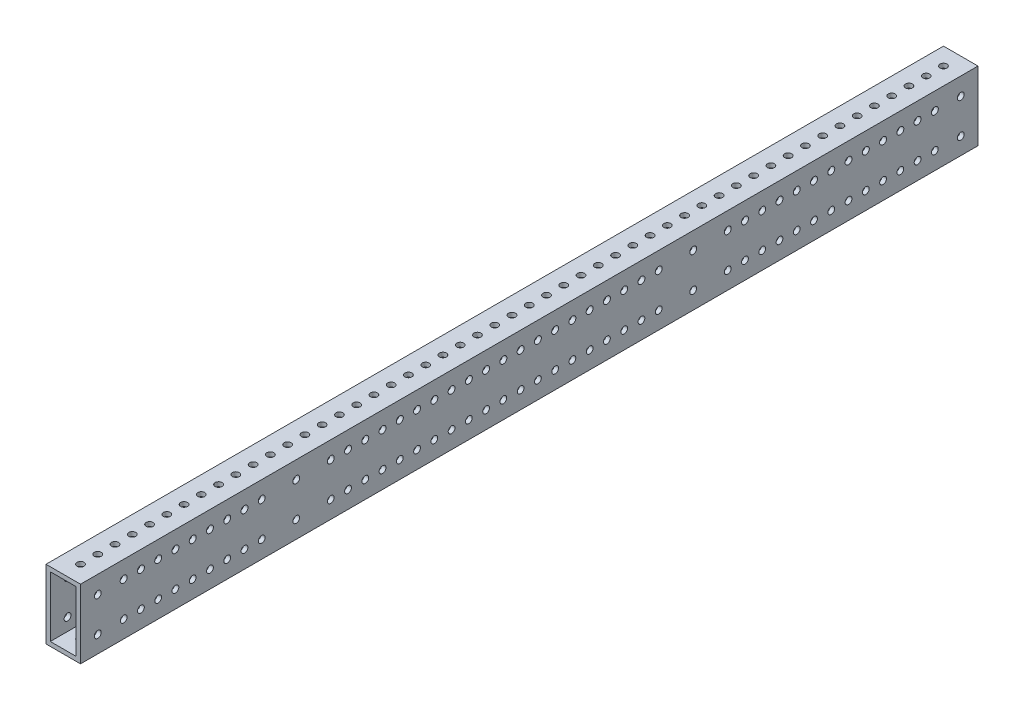
SolidWorks part; units mm, degrees
material "6061-T6 (SS)"
ref_plane "Front Plane" through (0, 0, 0) normal (0, 0, 1) x (1, 0, 0)
ref_plane "Top Plane" through (0, 0, 0) normal (0, 1, 0) x (1, 0, 0)
ref_plane "Right Plane" through (0, 0, 0) normal (1, 0, 0) x (0, 0, -1)
sketch "Sketch1" plane through (0, 0, 0) normal (0, 0, 1) x (1, 0, 0)
  line L0 (-9.525, 22.225) -> (9.525, 22.225)
  line L1 (-12.7, 25.4) -> (12.7, 25.4)
  line L2 (-12.7, 25.4) -> (-12.7, -25.4)
  line L3 (-12.7, -25.4) -> (12.7, -25.4)
  line L4 (12.7, 25.4) -> (12.7, -25.4)
  line L5 (9.525, 22.225) -> (9.525, -22.225)
  line L6 (-9.525, -22.225) -> (9.525, -22.225)
  line L7 (-9.525, 22.225) -> (-9.525, -22.225)
  line L8 (-12.7, 25.4) -> (12.7, -25.4) construction
  line L9 (12.7, 25.4) -> (-12.7, -25.4) construction
  point P5 (0, 0)
  dimension "D1" = 25.4
  dimension "D2" = 50.8
  dimension "D3" = 3.175
extrude "Boss-Extrude1" add sketch "Sketch1" along normal mid plane 660.4
sketch "Sketch2" plane through (0, 25.4, 0) normal (0, 1, 0) x (1, 0, 0)
  line L0 (12.7, -330.2) -> (-12.7, -330.2) construction
  line L1 (-12.7, -330.2) -> (-12.7, 330.2) construction
  line L4 (12.7, 330.2) -> (-12.7, 330.2) construction
  circle A0 centre (0, -317.5) radius 2.5527 construction
  circle A1 centre (25.4, -292.1) radius 2.5527 construction
  circle A2 centre (0, -317.5) radius 2.5527
  circle A3 centre (0, -304.8) radius 2.5527
  circle A4 centre (0, -304.8) radius 2.5527 construction
  circle A5 centre (25.4, -279.4) radius 2.5527 construction
  circle A6 centre (0, -292.1) radius 2.5527
  circle A7 centre (0, -292.1) radius 2.5527 construction
  circle A8 centre (25.4, -266.7) radius 2.5527 construction
  circle A9 centre (0, -279.4) radius 2.5527
  circle A10 centre (0, -279.4) radius 2.5527 construction
  circle A11 centre (25.4, -254) radius 2.5527 construction
  circle A12 centre (0, -266.7) radius 2.5527
  circle A13 centre (0, -266.7) radius 2.5527 construction
  circle A14 centre (25.4, -241.3) radius 2.5527 construction
  circle A15 centre (0, -254) radius 2.5527
  circle A16 centre (0, -254) radius 2.5527 construction
  circle A17 centre (25.4, -228.6) radius 2.5527 construction
  circle A18 centre (0, -241.3) radius 2.5527
  circle A19 centre (0, -241.3) radius 2.5527 construction
  circle A20 centre (25.4, -215.9) radius 2.5527 construction
  circle A21 centre (0, -228.6) radius 2.5527
  circle A22 centre (0, -228.6) radius 2.5527 construction
  circle A23 centre (25.4, -203.2) radius 2.5527 construction
  circle A24 centre (0, -215.9) radius 2.5527
  circle A25 centre (0, -215.9) radius 2.5527 construction
  circle A26 centre (25.4, -190.5) radius 2.5527 construction
  circle A27 centre (0, -203.2) radius 2.5527
  circle A28 centre (0, -203.2) radius 2.5527 construction
  circle A29 centre (25.4, -177.8) radius 2.5527 construction
  circle A30 centre (0, -190.5) radius 2.5527
  circle A31 centre (0, -190.5) radius 2.5527 construction
  circle A32 centre (25.4, -165.1) radius 2.5527 construction
  circle A33 centre (0, -177.8) radius 2.5527
  circle A34 centre (0, -177.8) radius 2.5527 construction
  circle A35 centre (25.4, -152.4) radius 2.5527 construction
  circle A36 centre (0, -165.1) radius 2.5527
  circle A37 centre (0, -165.1) radius 2.5527 construction
  circle A38 centre (25.4, -139.7) radius 2.5527 construction
  circle A39 centre (0, -152.4) radius 2.5527
  circle A40 centre (0, -152.4) radius 2.5527 construction
  circle A41 centre (25.4, -127) radius 2.5527 construction
  circle A42 centre (0, -139.7) radius 2.5527
  circle A43 centre (0, -139.7) radius 2.5527 construction
  circle A44 centre (25.4, -114.3) radius 2.5527 construction
  circle A45 centre (0, -127) radius 2.5527
  circle A46 centre (0, -127) radius 2.5527 construction
  circle A47 centre (25.4, -101.6) radius 2.5527 construction
  circle A48 centre (0, -114.3) radius 2.5527
  circle A49 centre (0, -114.3) radius 2.5527 construction
  circle A50 centre (25.4, -88.9) radius 2.5527 construction
  circle A51 centre (0, -101.6) radius 2.5527
  circle A52 centre (0, -101.6) radius 2.5527 construction
  circle A53 centre (25.4, -76.2) radius 2.5527 construction
  circle A54 centre (0, -88.9) radius 2.5527
  circle A55 centre (0, -88.9) radius 2.5527 construction
  circle A56 centre (25.4, -63.5) radius 2.5527 construction
  circle A57 centre (0, -76.2) radius 2.5527
  circle A58 centre (0, -76.2) radius 2.5527 construction
  circle A59 centre (25.4, -50.8) radius 2.5527 construction
  circle A60 centre (0, -63.5) radius 2.5527
  circle A61 centre (0, -63.5) radius 2.5527 construction
  circle A62 centre (25.4, -38.1) radius 2.5527 construction
  circle A63 centre (0, -50.8) radius 2.5527
  circle A64 centre (0, -50.8) radius 2.5527 construction
  circle A65 centre (25.4, -25.4) radius 2.5527 construction
  circle A66 centre (0, -38.1) radius 2.5527
  circle A67 centre (0, -38.1) radius 2.5527 construction
  circle A68 centre (25.4, -12.7) radius 2.5527 construction
  circle A69 centre (0, -25.4) radius 2.5527
  circle A70 centre (0, -25.4) radius 2.5527 construction
  circle A71 centre (25.4, 0) radius 2.5527 construction
  circle A72 centre (0, -12.7) radius 2.5527
  circle A73 centre (0, -12.7) radius 2.5527 construction
  circle A74 centre (25.4, 12.7) radius 2.5527 construction
  circle A75 centre (0, 0) radius 2.5527
  circle A76 centre (0, 0) radius 2.5527 construction
  circle A77 centre (25.4, 25.4) radius 2.5527 construction
  circle A78 centre (0, 12.7) radius 2.5527
  circle A79 centre (0, 12.7) radius 2.5527 construction
  circle A80 centre (25.4, 38.1) radius 2.5527 construction
  circle A81 centre (0, 25.4) radius 2.5527
  circle A82 centre (0, 25.4) radius 2.5527 construction
  circle A83 centre (25.4, 50.8) radius 2.5527 construction
  circle A84 centre (0, 38.1) radius 2.5527
  circle A85 centre (0, 38.1) radius 2.5527 construction
  circle A86 centre (25.4, 63.5) radius 2.5527 construction
  circle A87 centre (0, 50.8) radius 2.5527
  circle A88 centre (0, 50.8) radius 2.5527 construction
  circle A89 centre (25.4, 76.2) radius 2.5527 construction
  circle A90 centre (0, 63.5) radius 2.5527
  circle A91 centre (0, 63.5) radius 2.5527 construction
  circle A92 centre (25.4, 88.9) radius 2.5527 construction
  circle A93 centre (0, 76.2) radius 2.5527
  circle A94 centre (0, 76.2) radius 2.5527 construction
  circle A95 centre (25.4, 101.6) radius 2.5527 construction
  circle A96 centre (0, 88.9) radius 2.5527
  circle A97 centre (0, 88.9) radius 2.5527 construction
  circle A98 centre (25.4, 114.3) radius 2.5527 construction
  circle A99 centre (0, 101.6) radius 2.5527
  circle A100 centre (0, 101.6) radius 2.5527 construction
  circle A101 centre (25.4, 127) radius 2.5527 construction
  circle A108 centre (0, 127) radius 2.5527 [skipped]
  circle A109 centre (0, 127) radius 2.5527 [skipped]
  circle A110 centre (25.4, 152.4) radius 2.5527 [skipped]
  circle A111 centre (0, 114.3) radius 2.5527 [skipped]
  circle A112 centre (0, 114.3) radius 2.5527 [skipped]
  circle A113 centre (25.4, 139.7) radius 2.5527 [skipped]
  circle A114 centre (25.4, 139.7) radius 2.5527 construction
  circle A115 centre (0, 114.3) radius 2.5527 construction
  circle A116 centre (0, 114.3) radius 2.5527
  circle A117 centre (25.4, 152.4) radius 2.5527 construction
  circle A118 centre (0, 127) radius 2.5527 construction
  circle A119 centre (0, 127) radius 2.5527
  circle A120 centre (25.4, 165.1) radius 2.5527 construction
  circle A121 centre (0, 139.7) radius 2.5527 construction
  circle A122 centre (0, 139.7) radius 2.5527
  circle A123 centre (25.4, 177.8) radius 2.5527 construction
  circle A124 centre (0, 152.4) radius 2.5527 construction
  circle A125 centre (0, 152.4) radius 2.5527
  circle A126 centre (25.4, 190.5) radius 2.5527 construction
  circle A127 centre (0, 165.1) radius 2.5527 construction
  circle A128 centre (0, 165.1) radius 2.5527
  circle A129 centre (25.4, 203.2) radius 2.5527 construction
  circle A130 centre (0, 177.8) radius 2.5527 construction
  circle A131 centre (0, 177.8) radius 2.5527
  circle A132 centre (25.4, 215.9) radius 2.5527 construction
  circle A133 centre (0, 190.5) radius 2.5527 construction
  circle A134 centre (0, 190.5) radius 2.5527
  circle A135 centre (25.4, 228.6) radius 2.5527 construction
  circle A136 centre (0, 203.2) radius 2.5527 construction
  circle A137 centre (0, 203.2) radius 2.5527
  circle A138 centre (25.4, 241.3) radius 2.5527 construction
  circle A139 centre (0, 215.9) radius 2.5527 construction
  circle A140 centre (0, 215.9) radius 2.5527
  circle A141 centre (25.4, 254) radius 2.5527 construction
  circle A142 centre (0, 228.6) radius 2.5527 construction
  circle A143 centre (0, 228.6) radius 2.5527
  circle A144 centre (25.4, 266.7) radius 2.5527 construction
  circle A145 centre (0, 241.3) radius 2.5527 construction
  circle A146 centre (0, 241.3) radius 2.5527
  circle A147 centre (25.4, 279.4) radius 2.5527 construction
  circle A148 centre (0, 254) radius 2.5527 construction
  circle A149 centre (0, 254) radius 2.5527
  circle A150 centre (25.4, 292.1) radius 2.5527 construction
  circle A151 centre (0, 266.7) radius 2.5527 construction
  circle A152 centre (0, 266.7) radius 2.5527
  circle A153 centre (0, 279.4) radius 2.5527
  circle A154 centre (0, 292.1) radius 2.5527
  circle A155 centre (0, 304.8) radius 2.5527
  circle A156 centre (0, 317.5) radius 2.5527
  dimension "D2" = 5.1054
  dimension "D4" = 12.7
  dimension "D9" = 12.7
  dimension "D11" = 12.7
  dimension "D12" = 12.7
  dimension "D1" = 12.7
  dimension "D3" = 12.7
  dimension "D6" = 12.7
  dimension "D7" = 228.6
  dimension "D5" = 36
  dimension "D8" = 14
  dimension "D10" = 5
extrude "Cut-Extrude1" cut sketch "Sketch2" against normal through all
sketch "Sketch4" plane through (12.7, 0, 0) normal (1, 0, 0) x (0, 0, -1)
  line L0 (-330.2, 25.4) -> (330.2, 25.4) construction
  line L1 (-330.2, -25.4) -> (-330.2, 25.4) construction
  line L2 (-330.2, -25.4) -> (330.2, -25.4) construction
  line L3 (-330.2, 25.4) -> (-330.2, -25.4) construction
  line L4 (-157.7381, 25.4) -> (-328.1801, 25.4) construction
  line L5 (-330.2, 25.4) -> (330.2, 25.4) construction
  line L6 (330.2, -25.4) -> (330.2, 25.4) construction
  circle A2 centre (-323.85, -12.7) radius 2.4892 construction
  circle A3 centre (-311.15, -12.7) radius 2.4892 construction
  circle A16 centre (-298.45, -12.7) radius 2.4892
  circle A17 centre (-285.75, -12.7) radius 2.4892
  circle A18 centre (-273.05, -12.7) radius 2.4892
  circle A19 centre (107.95, -12.7) radius 2.4892 construction
  circle A20 centre (120.65, -12.7) radius 2.4892
  circle A21 centre (133.35, -12.7) radius 2.4892 construction
  circle A22 centre (146.05, -12.7) radius 2.4892
  circle A23 centre (158.75, -12.7) radius 2.4892
  circle A24 centre (171.45, -12.7) radius 2.4892
  circle A25 centre (184.15, -12.7) radius 2.4892
  circle A26 centre (196.85, -12.7) radius 2.4892
  circle A27 centre (209.55, -12.7) radius 2.4892
  circle A28 centre (222.25, -12.7) radius 2.4892
  circle A29 centre (234.95, -12.7) radius 2.4892
  circle A30 centre (247.65, -12.7) radius 2.4892
  circle A31 centre (260.35, -12.7) radius 2.4892
  circle A32 centre (273.05, -12.7) radius 2.4892
  circle A33 centre (-323.85, 12.7) radius 2.5527 construction
  circle A34 centre (-311.15, 12.7) radius 2.5527 construction
  circle A35 centre (-260.35, -12.7) radius 2.4892
  circle A36 centre (-247.65, -12.7) radius 2.4892
  circle A37 centre (-234.95, -12.7) radius 2.4892
  circle A38 centre (-222.25, -12.7) radius 2.4892
  circle A39 centre (-209.55, -12.7) radius 2.4892
  circle A40 centre (-196.85, -12.7) radius 2.4892
  circle A41 centre (-184.15, -12.7) radius 2.4892 construction
  circle A42 centre (-171.45, -12.7) radius 2.4892
  circle A43 centre (-158.75, -12.7) radius 2.4892 construction
  circle A44 centre (-146.05, -12.7) radius 2.4892
  circle A45 centre (-133.35, -12.7) radius 2.4892
  circle A46 centre (-120.65, -12.7) radius 2.4892
  circle A47 centre (-107.95, -12.7) radius 2.4892
  circle A48 centre (-95.25, -12.7) radius 2.4892
  circle A49 centre (-82.55, -12.7) radius 2.4892
  circle A50 centre (-69.85, -12.7) radius 2.4892
  circle A51 centre (-57.15, -12.7) radius 2.4892
  circle A52 centre (-44.45, -12.7) radius 2.4892
  circle A53 centre (-31.75, -12.7) radius 2.4892
  circle A54 centre (-19.05, -12.7) radius 2.4892
  circle A55 centre (-6.35, -12.7) radius 2.4892
  circle A56 centre (6.35, -12.7) radius 2.4892
  circle A57 centre (19.05, -12.7) radius 2.4892
  circle A58 centre (31.75, -12.7) radius 2.4892
  circle A59 centre (44.45, -12.7) radius 2.4892
  circle A60 centre (57.15, -12.7) radius 2.4892
  circle A61 centre (69.85, -12.7) radius 2.4892
  circle A62 centre (82.55, -12.7) radius 2.4892
  circle A63 centre (95.25, -12.7) radius 2.4892
  circle A64 centre (-298.45, 12.7) radius 2.5527
  circle A65 centre (-285.75, 12.7) radius 2.5527
  circle A66 centre (-273.05, 12.7) radius 2.5527
  circle A67 centre (-260.35, 12.7) radius 2.5527
  circle A68 centre (-247.65, 12.7) radius 2.5527
  circle A69 centre (-234.95, 12.7) radius 2.5527
  circle A70 centre (-222.25, 12.7) radius 2.5527
  circle A71 centre (-209.55, 12.7) radius 2.5527
  circle A72 centre (-196.85, 12.7) radius 2.5527
  circle A73 centre (-184.15, 12.7) radius 2.5527 construction
  circle A74 centre (-171.45, 12.7) radius 2.5527
  circle A75 centre (-158.75, 12.7) radius 2.5527 construction
  circle A76 centre (-146.05, 12.7) radius 2.5527
  circle A77 centre (-133.35, 12.7) radius 2.5527
  circle A78 centre (-120.65, 12.7) radius 2.5527
  circle A79 centre (-107.95, 12.7) radius 2.5527
  circle A80 centre (-95.25, 12.7) radius 2.5527
  circle A81 centre (-82.55, 12.7) radius 2.5527
  circle A82 centre (-69.85, 12.7) radius 2.5527
  circle A83 centre (-57.15, 12.7) radius 2.5527
  circle A84 centre (-44.45, 12.7) radius 2.5527
  circle A85 centre (-31.75, 12.7) radius 2.5527
  circle A86 centre (-19.05, 12.7) radius 2.5527
  circle A87 centre (-6.35, 12.7) radius 2.5527
  circle A88 centre (6.35, 12.7) radius 2.5527
  circle A89 centre (19.05, 12.7) radius 2.5527
  circle A90 centre (31.75, 12.7) radius 2.5527
  circle A91 centre (44.45, 12.7) radius 2.5527
  circle A92 centre (57.15, 12.7) radius 2.5527
  circle A93 centre (69.85, 12.7) radius 2.5527
  circle A94 centre (82.55, 12.7) radius 2.5527
  circle A95 centre (95.25, 12.7) radius 2.5527
  circle A96 centre (107.95, 12.7) radius 2.5527 construction
  circle A97 centre (120.65, 12.7) radius 2.5527
  circle A98 centre (133.35, 12.7) radius 2.5527 construction
  circle A99 centre (146.05, 12.7) radius 2.5527
  circle A100 centre (158.75, 12.7) radius 2.5527
  circle A101 centre (171.45, 12.7) radius 2.5527
  circle A102 centre (184.15, 12.7) radius 2.5527
  circle A103 centre (196.85, 12.7) radius 2.5527
  circle A104 centre (209.55, 12.7) radius 2.5527
  circle A105 centre (222.25, 12.7) radius 2.5527
  circle A106 centre (234.95, 12.7) radius 2.5527
  circle A107 centre (247.65, 12.7) radius 2.5527
  circle A108 centre (260.35, 12.7) radius 2.5527
  circle A109 centre (273.05, 12.7) radius 2.5527
  circle A110 centre (285.75, 12.7) radius 2.5527
  circle A111 centre (285.75, -12.7) radius 2.4892
  circle A112 centre (298.45, 12.7) radius 2.5527
  circle A113 centre (298.45, -12.7) radius 2.4892
  circle A114 centre (311.15, 12.7) radius 2.5527 construction
  circle A115 centre (311.15, -12.7) radius 2.4892 construction
  circle A116 centre (323.85, 12.7) radius 2.5527 construction
  circle A117 centre (323.85, -12.7) radius 2.4892 construction
  circle A118 centre (-317.5, 12.446) radius 2.5527
  circle A122 centre (-317.5, -12.954) radius 2.5527
  circle A123 centre (317.5, 12.446) radius 2.5527
  circle A124 centre (317.5, -12.954) radius 2.5527
  dimension "D2" = 4.9784
  dimension "D1" = 6.35
  dimension "D8" = 5.1054
  dimension "D9" = 12.7
  dimension "D10" = 6.35
  dimension "D11" = 48
  dimension "D12" = 12.7
  dimension "D13" = 12.7
  dimension "D14" = 12.7
  dimension "D16" = 12.7
  dimension "D17" = 12.954
  dimension "D18" = 5.1054
  dimension "D19" = 12.7
  dimension "D21" = 12.446
  dimension "D22" = 5.1054
  dimension "D23" = 12.954
  dimension "D24" = 12.7
  dimension "D26" = 12.446
  dimension "D3" = 12.7
  dimension "D4" = 12.7
  dimension "D5" = 34
  dimension "D6" = 10
  dimension "D7" = 6
  dimension "D15" = 5
  dimension "D20" = 2
  dimension "D25" = 2
extrude "Cut-Extrude3" cut sketch "Sketch4" against normal through all
